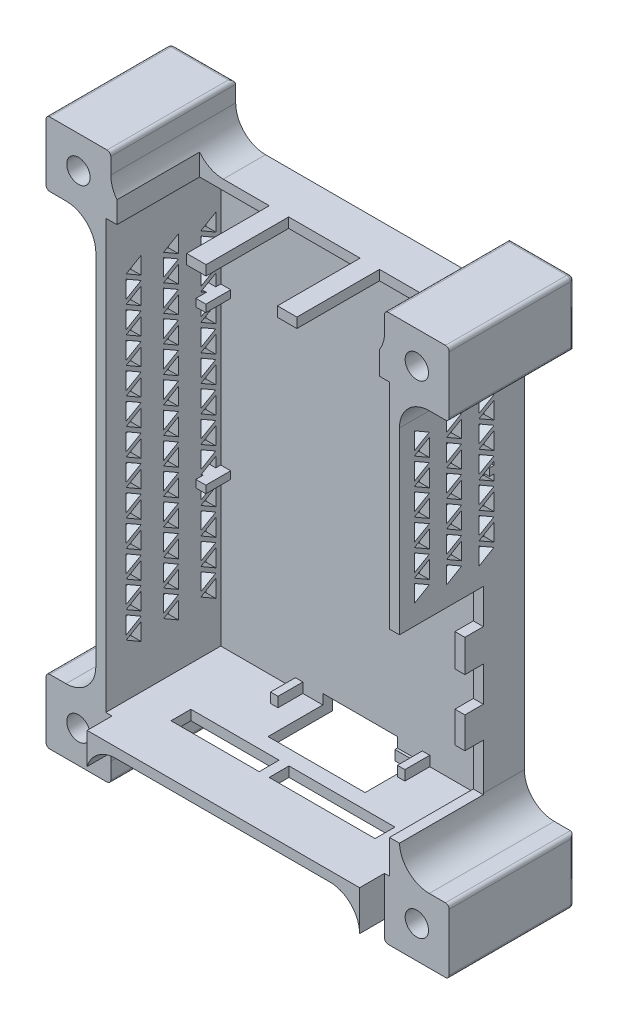
SolidWorks part; units mm, degrees
ref_plane "Front Plane" through (0, 0, 0) normal (0, 0, 1) x (1, 0, 0)
ref_plane "Top Plane" through (0, 0, 0) normal (0, 1, 0) x (1, 0, 0)
ref_plane "Right Plane" through (0, 0, 0) normal (1, 0, 0) x (0, 0, -1)
sketch "Sketch1" plane through (0, 0, 0) normal (0, 0, 1) x (1, 0, 0)
  line L1 (0, 0) -> (61, 0)
  line L2 (0, 0) -> (0, 90)
  line L3 (0, 90) -> (61, 90)
  line L4 (61, 0) -> (61, 90)
  dimension "D1" = 61
  dimension "D2" = 90
extrude "Boss-Extrude1" add sketch "Sketch1" along normal blind 2
sketch "Sketch2" plane through (0, 0, 2) normal (0, 0, 1) x (1, 0, 0)
  line L7 (0, -16.225) -> (0, 16.225) construction
  line L8 (0, 90) -> (0, 0)
  line L9 (2, 90) -> (2, 2)
  line L10 (2, 2) -> (59, 2)
  line L11 (59, 2) -> (59, 90)
  line L12 (2, 88) -> (2, 2)
  line L13 (2, 2) -> (59, 2)
  line L14 (59, 2) -> (59, 88)
  line L15 (0, 0) -> (61, 0)
  line L18 (61, 90) -> (61, 0)
  line L20 (2, 88) -> (59, 88)
  line L21 (0, 90) -> (61, 90)
  dimension "D1" = 2
extrude "Boss-Extrude2" add sketch "Sketch2" along normal blind 6.6
sketch "Sketch3" plane through (0, 0, 2) normal (0, 0, 1) x (1, 0, 0)
  line L0 (59, 2) -> (2, 2) construction
  line L1 (44, 2) -> (42.5, 2)
  line L2 (44, 2) -> (44, 4)
  line L3 (44, 4) -> (42.5, 4)
  line L4 (42.5, 2) -> (42.5, 4)
  line L5 (2, 2) -> (2, 88) construction
  line L6 (17, 2) -> (18.5, 2)
  line L7 (17, 2) -> (17, 4)
  line L8 (17, 4) -> (18.5, 4)
  line L9 (18.5, 2) -> (18.5, 4)
  line L10 (2, 32) -> (4, 32)
  line L11 (2, 32) -> (2, 33.5)
  line L12 (2, 33.5) -> (4, 33.5)
  line L13 (4, 32) -> (4, 33.5)
  line L14 (59, 88) -> (59, 2) construction
  line L15 (59, 32) -> (57, 32)
  line L16 (59, 32) -> (59, 33.5)
  line L17 (59, 33.5) -> (57, 33.5)
  line L18 (57, 32) -> (57, 33.5)
  line L19 (2, 2) -> (2, 88) construction
  line L20 (59, 63.5) -> (57, 63.5)
  line L21 (59, 63.5) -> (59, 65)
  line L22 (59, 65) -> (57, 65)
  line L23 (57, 63.5) -> (57, 65)
  line L24 (2, 63.5) -> (4, 63.5)
  line L25 (2, 63.5) -> (2, 65)
  line L26 (2, 65) -> (4, 65)
  line L27 (4, 63.5) -> (4, 65)
  line L28 (59, 2) -> (2, 2) construction
  dimension "D1" = 1.5
  dimension "D2" = 1.5
  dimension "D3" = 1.5
  dimension "D4" = 1.5
  dimension "D5" = 1.5
  dimension "D6" = 1.5
  dimension "D7" = 2
  dimension "D8" = 2
  dimension "D9" = 2
  dimension "D10" = 2
  dimension "D11" = 2
  dimension "D12" = 2
  dimension "D13" = 30
  dimension "D14" = 30
  dimension "D15" = 30
  dimension "D16" = 30
  dimension "D17" = 15
  dimension "D18" = 15
extrude "Boss-Extrude3" add sketch "Sketch3" along normal blind 5
sketch "Sketch4" plane through (0, 0, 8.6) normal (0, 0, 1) x (1, 0, 0)
  line L1 (61, 90) -> (0, 90)
  line L3 (59, 88) -> (2, 88)
  line L5 (61, 90) -> (61, 0)
  line L6 (0, 90) -> (0, 0)
  line L7 (0, 0) -> (61, 0)
  line L8 (2, 2) -> (59, 2)
  line L9 (2, 88) -> (2, 2)
  line L10 (59, 2) -> (59, 88)
  line L11 (59, 2) -> (59, 88) construction
extrude "Boss-Extrude4" add sketch "Sketch4" along normal blind 16.5
sketch "Sketch5" plane through (0, 90, 0) normal (0, 1, 0) x (1, 0, 0)
  line L1 (57, -8.5) -> (40.4, -8.5)
  line L3 (57, -22.25) -> (40.4, -22.25) construction
  line L4 (40.4, -8.5) -> (40.4, -22.25)
  line L5 (61, 0) -> (0, 0) construction
  line L6 (61, -25.1) -> (0, -25.1) construction
  line L7 (36.5, -25.1) -> (22.15, -25.1)
  line L8 (36.5, -25.1) -> (36.5, -8.5)
  line L9 (36.5, -8.5) -> (22.15, -8.5)
  line L10 (22.15, -25.1) -> (22.15, -8.5)
  line L11 (0, -25.1) -> (0, 0) construction
  line L12 (18.25, -25.1) -> (4.25, -25.1)
  line L13 (18.25, -25.1) -> (18.25, -8.5)
  line L14 (18.25, -8.5) -> (4.25, -8.5)
  line L15 (4.25, -25.1) -> (4.25, -8.5)
  line L17 (57, -25.1) -> (40.4, -25.1)
  line L19 (57, -22.25) -> (40.4, -22.25) construction
  line L20 (40.4, -25.1) -> (40.4, -22.25)
  line L21 (57, -8.5) -> (57, -25.1)
  line L22 (61, -25.1) -> (61, 0) construction
  point P21 (61, -12.55)
  dimension "D2" = 16.6
  dimension "D3" = 13.75
  dimension "D4" = 8.5
  dimension "D5" = 4.25
  dimension "D6" = 3.9
  dimension "D7" = 14
  dimension "D8" = 8.5
  dimension "D9" = 8.5
  dimension "D10" = 3.9
  dimension "D11" = 4
  dimension "D12" = 0
extrude "Cut-Extrude1" cut sketch "Sketch5" against normal blind 2
sketch "Sketch7" plane through (61, 0, 0) normal (1, 0, 0) x (0, 0, -1)
  line L0 (-11.95, 18.25) -> (-11.95, 24.5)
  line L8 (-11.95, 18.25) -> (-8.25, 18.25)
  line L9 (-8.25, 8.75) -> (-8.25, 18.25)
  line L10 (-11.95, 24.5) -> (-8.25, 24.5)
  line L12 (-11.95, 38) -> (-8.25, 38)
  line L14 (-11.95, 31.5) -> (-8.25, 31.5)
  line L18 (-25.1, 0) -> (-25.1, 90) construction
  line L19 (-25.1, 8.75) -> (-25.1, 45)
  line L21 (-11.95, 38) -> (-11.95, 31.5)
  line L22 (-8.25, 8.75) -> (-25.1, 8.75)
  line L23 (-25.1, 45) -> (-8.25, 45)
  line L24 (-25.1, 0) -> (0, 0) construction
  line L25 (-8.25, 24.5) -> (-8.25, 31.5)
  line L26 (-8.25, 38) -> (-8.25, 45)
  line L28 (0, 0) -> (0, 90) construction
  line L47 (-22.1, 79) -> (-19.1, 77.2679)
  line L49 (-19.1, 77.2679) -> (-22.1, 75.5359)
  line L50 (-22.1, 75.5359) -> (-22.1, 79)
  line L141 (-22.1, 74.6121) -> (-19.1, 76.3442)
  line L144 (-19.1, 76.3442) -> (-19.1, 72.8801)
  line L145 (-19.1, 72.8801) -> (-22.1, 74.6121)
  line L146 (-25.1, 90) -> (0, 90) construction
  line L151 (-15.6, 75.5359) -> (-15.6, 79)
  line L152 (-15.6, 79) -> (-12.6, 77.2679)
  line L153 (-12.6, 77.2679) -> (-15.6, 75.5359)
  line L154 (-12.6, 72.8801) -> (-15.6, 74.6121)
  line L155 (-15.6, 74.6121) -> (-12.6, 76.3442)
  line L156 (-12.6, 76.3442) -> (-12.6, 72.8801)
  line L157 (-9.1, 75.5359) -> (-9.1, 79)
  line L158 (-9.1, 79) -> (-6.1, 77.2679)
  line L159 (-6.1, 77.2679) -> (-9.1, 75.5359)
  line L160 (-6.1, 72.8801) -> (-9.1, 74.6121)
  line L161 (-9.1, 74.6121) -> (-6.1, 76.3442)
  line L162 (-6.1, 76.3442) -> (-6.1, 72.8801)
  line L163 (-15.6, 70.2243) -> (-15.6, 73.6884)
  line L164 (-15.6, 73.6884) -> (-12.6, 71.9563)
  line L165 (-12.6, 71.9563) -> (-15.6, 70.2243)
  line L166 (-12.6, 67.5685) -> (-15.6, 69.3005)
  line L167 (-15.6, 69.3005) -> (-12.6, 71.0326)
  line L168 (-12.6, 71.0326) -> (-12.6, 67.5685)
  line L169 (-9.1, 70.2243) -> (-9.1, 73.6884)
  line L170 (-9.1, 73.6884) -> (-6.1, 71.9563)
  line L171 (-6.1, 71.9563) -> (-9.1, 70.2243)
  line L172 (-6.1, 67.5685) -> (-9.1, 69.3005)
  line L173 (-9.1, 69.3005) -> (-6.1, 71.0326)
  line L174 (-6.1, 71.0326) -> (-6.1, 67.5685)
  line L175 (-15.6, 64.9127) -> (-15.6, 68.3768)
  line L176 (-15.6, 68.3768) -> (-12.6, 66.6447)
  line L177 (-12.6, 66.6447) -> (-15.6, 64.9127)
  line L178 (-12.6, 62.2568) -> (-15.6, 63.9889)
  line L179 (-15.6, 63.9889) -> (-12.6, 65.7209)
  line L180 (-12.6, 65.7209) -> (-12.6, 62.2568)
  line L181 (-9.1, 64.9127) -> (-9.1, 68.3768)
  line L182 (-9.1, 68.3768) -> (-6.1, 66.6447)
  line L183 (-6.1, 66.6447) -> (-9.1, 64.9127)
  line L184 (-6.1, 62.2568) -> (-9.1, 63.9889)
  line L185 (-9.1, 63.9889) -> (-6.1, 65.7209)
  line L186 (-6.1, 65.7209) -> (-6.1, 62.2568)
  line L187 (-15.6, 59.601) -> (-15.6, 63.0651)
  line L188 (-15.6, 63.0651) -> (-12.6, 61.3331)
  line L189 (-12.6, 61.3331) -> (-15.6, 59.601)
  line L190 (-12.6, 56.9452) -> (-15.6, 58.6773)
  line L191 (-15.6, 58.6773) -> (-12.6, 60.4093)
  line L192 (-12.6, 60.4093) -> (-12.6, 56.9452)
  line L193 (-9.1, 59.601) -> (-9.1, 63.0651)
  line L194 (-9.1, 63.0651) -> (-6.1, 61.3331)
  line L195 (-6.1, 61.3331) -> (-9.1, 59.601)
  line L196 (-6.1, 56.9452) -> (-9.1, 58.6773)
  line L197 (-9.1, 58.6773) -> (-6.1, 60.4093)
  line L198 (-6.1, 60.4093) -> (-6.1, 56.9452)
  line L199 (-15.6, 54.2894) -> (-15.6, 57.7535)
  line L200 (-15.6, 57.7535) -> (-12.6, 56.0215)
  line L201 (-12.6, 56.0215) -> (-15.6, 54.2894)
  line L202 (-12.6, 51.6336) -> (-15.6, 53.3656)
  line L203 (-15.6, 53.3656) -> (-12.6, 55.0977)
  line L204 (-12.6, 55.0977) -> (-12.6, 51.6336)
  line L205 (-9.1, 54.2894) -> (-9.1, 57.7535)
  line L206 (-9.1, 57.7535) -> (-6.1, 56.0215)
  line L207 (-6.1, 56.0215) -> (-9.1, 54.2894)
  line L208 (-6.1, 51.6336) -> (-9.1, 53.3656)
  line L209 (-9.1, 53.3656) -> (-6.1, 55.0977)
  line L210 (-6.1, 55.0977) -> (-6.1, 51.6336)
  line L211 (-15.6, 48.9778) -> (-15.6, 52.4419)
  line L212 (-15.6, 52.4419) -> (-12.6, 50.7098)
  line L213 (-12.6, 50.7098) -> (-15.6, 48.9778)
  line L217 (-9.1, 48.9778) -> (-9.1, 52.4419)
  line L218 (-9.1, 52.4419) -> (-6.1, 50.7098)
  line L219 (-6.1, 50.7098) -> (-9.1, 48.9778)
  line L223 (-22.1, 70.2243) -> (-22.1, 73.6884)
  line L224 (-22.1, 73.6884) -> (-19.1, 71.9563)
  line L225 (-19.1, 71.9563) -> (-22.1, 70.2243)
  line L226 (-19.1, 67.5685) -> (-22.1, 69.3005)
  line L227 (-22.1, 69.3005) -> (-19.1, 71.0326)
  line L228 (-19.1, 71.0326) -> (-19.1, 67.5685)
  line L229 (-22.1, 64.9127) -> (-22.1, 68.3768)
  line L230 (-22.1, 68.3768) -> (-19.1, 66.6447)
  line L231 (-19.1, 66.6447) -> (-22.1, 64.9127)
  line L232 (-19.1, 62.2568) -> (-22.1, 63.9889)
  line L233 (-22.1, 63.9889) -> (-19.1, 65.7209)
  line L234 (-19.1, 65.7209) -> (-19.1, 62.2568)
  line L235 (-22.1, 59.601) -> (-22.1, 63.0651)
  line L236 (-22.1, 63.0651) -> (-19.1, 61.3331)
  line L237 (-19.1, 61.3331) -> (-22.1, 59.601)
  line L238 (-19.1, 56.9452) -> (-22.1, 58.6773)
  line L239 (-22.1, 58.6773) -> (-19.1, 60.4093)
  line L240 (-19.1, 60.4093) -> (-19.1, 56.9452)
  line L241 (-22.1, 54.2894) -> (-22.1, 57.7535)
  line L242 (-22.1, 57.7535) -> (-19.1, 56.0215)
  line L243 (-19.1, 56.0215) -> (-22.1, 54.2894)
  line L244 (-19.1, 51.6336) -> (-22.1, 53.3656)
  line L245 (-22.1, 53.3656) -> (-19.1, 55.0977)
  line L246 (-19.1, 55.0977) -> (-19.1, 51.6336)
  line L247 (-22.1, 48.9778) -> (-22.1, 52.4419)
  line L248 (-22.1, 52.4419) -> (-19.1, 50.7098)
  line L249 (-19.1, 50.7098) -> (-22.1, 48.9778)
  line L253 (-6.1, 49.7861) -> (-6.1, 46.322) [skipped]
  line L254 (-9.1, 48.054) -> (-6.1, 49.7861) [skipped]
  line L255 (-12.6, 49.7861) -> (-12.6, 46.322) [skipped]
  line L256 (-15.6, 48.054) -> (-12.6, 49.7861) [skipped]
  line L257 (-19.1, 49.7861) -> (-19.1, 46.322) [skipped]
  line L258 (-22.1, 48.054) -> (-19.1, 49.7861) [skipped]
  line L259 (-19.1, 46.322) -> (-22.1, 48.054) [skipped]
  line L260 (-12.6, 46.322) -> (-15.6, 48.054) [skipped]
  line L261 (-6.1, 46.322) -> (-9.1, 48.054) [skipped]
  point P0 (-8.25, 13.5)
  point P16 (-8.25, 41.5)
  point P18 (-10.1, 18.25)
  point P20 (-8.25, 28)
  dimension "D1" = 9.5
  dimension "D2" = 28
  dimension "D3" = 7
  dimension "D4" = 7
  dimension "D5" = 13.5
  dimension "D6" = 41.5
  dimension "D7" = 3.7
  dimension "D8" = 3.7
  dimension "D9" = 8.25
  dimension "D10" = 0
  dimension "D11" = 0
  dimension "D12" = 60
  dimension "D13" = 60
  dimension "D14" = 60
  dimension "D15" = 60
  dimension "D16" = 0.9238
  dimension "D17" = 3
  dimension "D18" = 11
  dimension "D19" = 3
  dimension "D20" = 3
  dimension "D21" = 6
  dimension "D22" = 0.9238
  dimension "D23" = 3
  dimension "D24" = 9.5
sketch "Sketch8" plane through (0, 0, 0) normal (0, -1, 0) x (-1, 0, 0)
  line L0 (0, -25.1) -> (0, 0) construction
  line L2 (-22.5, -13) -> (-22.5, -2.5)
  line L3 (-22.5, -2.5) -> (-42, -2.5)
  line L4 (-42, -13) -> (-42, -2.5)
  line L5 (0, 13.805) -> (0, -13.805) construction
  line L6 (-61, -25.1) -> (-61, 0) construction
  line L7 (-33.55, 0) -> (33.55, 0) construction
  line L8 (-22.5, -13) -> (-42, -13)
  line L9 (-10, -20) -> (-27.72, -20)
  line L10 (-10, -20) -> (-10, -16)
  line L11 (-10, -16) -> (-27.72, -16)
  line L12 (-51, -20) -> (-51, -16)
  line L13 (-27.72, -20) -> (-27.72, -16)
  line L14 (-29.72, -20) -> (-29.72, -16)
  line L15 (-29.72, -20) -> (-51, -20)
  line L16 (-29.72, -16) -> (-51, -16)
  dimension "D1" = 22.5
  dimension "D2" = 19
  dimension "D3" = 2.5
  dimension "D4" = 10.5
  dimension "D5" = 3
  dimension "D6" = 4
  dimension "D7" = 10
  dimension "D8" = 10
  dimension "D9" = 2
  dimension "D10" = 31.28
extrude "Cut-Extrude3" cut sketch "Sketch8" against normal blind 2
sketch "Sketch9" plane through (0, 0, 0) normal (-1, 0, 0) x (0, 0, 1)
  line L0 (3, 78) -> (6, 76.2679)
  line L5 (6, 76.2679) -> (3, 74.5359)
  line L6 (3, 74.5359) -> (3, 78)
  line L7 (3, 73.6121) -> (6, 75.3442)
  line L20 (6, 75.3442) -> (6, 71.8801)
  line L22 (6, 71.8801) -> (3, 73.6121)
  line L24 (0, 90) -> (0, 0) construction
  line L215 (25.1, 90) -> (0, 90) construction
  line L232 (10.5, 74.5359) -> (10.5, 78)
  line L236 (10.5, 78) -> (13.5, 76.2679)
  line L238 (13.5, 76.2679) -> (10.5, 74.5359)
  line L267 (13.5, 71.8801) -> (10.5, 73.6121)
  line L268 (10.5, 73.6121) -> (13.5, 75.3442)
  line L269 (13.5, 75.3442) -> (13.5, 71.8801)
  line L270 (18, 74.5359) -> (18, 78)
  line L271 (18, 78) -> (21, 76.2679)
  line L272 (21, 76.2679) -> (18, 74.5359)
  line L273 (21, 71.8801) -> (18, 73.6121)
  line L274 (18, 73.6121) -> (21, 75.3442)
  line L275 (21, 75.3442) -> (21, 71.8801)
  line L276 (10.5, 69.2243) -> (10.5, 72.6884)
  line L277 (10.5, 72.6884) -> (13.5, 70.9563)
  line L278 (13.5, 70.9563) -> (10.5, 69.2243)
  line L279 (13.5, 66.5685) -> (10.5, 68.3005)
  line L280 (10.5, 68.3005) -> (13.5, 70.0326)
  line L281 (13.5, 70.0326) -> (13.5, 66.5685)
  line L282 (18, 69.2243) -> (18, 72.6884)
  line L283 (18, 72.6884) -> (21, 70.9563)
  line L284 (21, 70.9563) -> (18, 69.2243)
  line L285 (21, 66.5685) -> (18, 68.3005)
  line L286 (18, 68.3005) -> (21, 70.0326)
  line L287 (21, 70.0326) -> (21, 66.5685)
  line L288 (10.5, 63.9127) -> (10.5, 67.3768)
  line L289 (10.5, 67.3768) -> (13.5, 65.6447)
  line L290 (13.5, 65.6447) -> (10.5, 63.9127)
  line L291 (13.5, 61.2568) -> (10.5, 62.9889)
  line L292 (10.5, 62.9889) -> (13.5, 64.7209)
  line L293 (13.5, 64.7209) -> (13.5, 61.2568)
  line L294 (18, 63.9127) -> (18, 67.3768)
  line L295 (18, 67.3768) -> (21, 65.6447)
  line L296 (21, 65.6447) -> (18, 63.9127)
  line L297 (21, 61.2568) -> (18, 62.9889)
  line L298 (18, 62.9889) -> (21, 64.7209)
  line L299 (21, 64.7209) -> (21, 61.2568)
  line L300 (10.5, 58.601) -> (10.5, 62.0651)
  line L301 (10.5, 62.0651) -> (13.5, 60.3331)
  line L302 (13.5, 60.3331) -> (10.5, 58.601)
  line L303 (13.5, 55.9452) -> (10.5, 57.6773)
  line L304 (10.5, 57.6773) -> (13.5, 59.4093)
  line L305 (13.5, 59.4093) -> (13.5, 55.9452)
  line L306 (18, 58.601) -> (18, 62.0651)
  line L307 (18, 62.0651) -> (21, 60.3331)
  line L308 (21, 60.3331) -> (18, 58.601)
  line L309 (21, 55.9452) -> (18, 57.6773)
  line L310 (18, 57.6773) -> (21, 59.4093)
  line L311 (21, 59.4093) -> (21, 55.9452)
  line L312 (10.5, 53.2894) -> (10.5, 56.7535)
  line L313 (10.5, 56.7535) -> (13.5, 55.0215)
  line L314 (13.5, 55.0215) -> (10.5, 53.2894)
  line L315 (13.5, 50.6336) -> (10.5, 52.3656)
  line L316 (10.5, 52.3656) -> (13.5, 54.0977)
  line L317 (13.5, 54.0977) -> (13.5, 50.6336)
  line L318 (18, 53.2894) -> (18, 56.7535)
  line L319 (18, 56.7535) -> (21, 55.0215)
  line L320 (21, 55.0215) -> (18, 53.2894)
  line L321 (21, 50.6336) -> (18, 52.3656)
  line L322 (18, 52.3656) -> (21, 54.0977)
  line L323 (21, 54.0977) -> (21, 50.6336)
  line L324 (10.5, 47.9778) -> (10.5, 51.4419)
  line L325 (10.5, 51.4419) -> (13.5, 49.7098)
  line L326 (13.5, 49.7098) -> (10.5, 47.9778)
  line L327 (13.5, 45.322) -> (10.5, 47.054)
  line L328 (10.5, 47.054) -> (13.5, 48.7861)
  line L329 (13.5, 48.7861) -> (13.5, 45.322)
  line L330 (18, 47.9778) -> (18, 51.4419)
  line L331 (18, 51.4419) -> (21, 49.7098)
  line L332 (21, 49.7098) -> (18, 47.9778)
  line L333 (21, 45.322) -> (18, 47.054)
  line L334 (18, 47.054) -> (21, 48.7861)
  line L335 (21, 48.7861) -> (21, 45.322)
  line L336 (10.5, 42.6662) -> (10.5, 46.1303)
  line L337 (10.5, 46.1303) -> (13.5, 44.3982)
  line L338 (13.5, 44.3982) -> (10.5, 42.6662)
  line L339 (13.5, 40.0104) -> (10.5, 41.7424)
  line L340 (10.5, 41.7424) -> (13.5, 43.4745)
  line L341 (13.5, 43.4745) -> (13.5, 40.0104)
  line L342 (18, 42.6662) -> (18, 46.1303)
  line L343 (18, 46.1303) -> (21, 44.3982)
  line L344 (21, 44.3982) -> (18, 42.6662)
  line L345 (21, 40.0104) -> (18, 41.7424)
  line L346 (18, 41.7424) -> (21, 43.4745)
  line L347 (21, 43.4745) -> (21, 40.0104)
  line L348 (10.5, 37.3545) -> (10.5, 40.8186)
  line L349 (10.5, 40.8186) -> (13.5, 39.0866)
  line L350 (13.5, 39.0866) -> (10.5, 37.3545)
  line L351 (13.5, 34.6987) -> (10.5, 36.4308)
  line L352 (10.5, 36.4308) -> (13.5, 38.1628)
  line L353 (13.5, 38.1628) -> (13.5, 34.6987)
  line L354 (18, 37.3545) -> (18, 40.8186)
  line L355 (18, 40.8186) -> (21, 39.0866)
  line L356 (21, 39.0866) -> (18, 37.3545)
  line L357 (21, 34.6987) -> (18, 36.4308)
  line L358 (18, 36.4308) -> (21, 38.1628)
  line L359 (21, 38.1628) -> (21, 34.6987)
  line L360 (10.5, 32.0429) -> (10.5, 35.507)
  line L361 (10.5, 35.507) -> (13.5, 33.775)
  line L362 (13.5, 33.775) -> (10.5, 32.0429)
  line L363 (13.5, 29.3871) -> (10.5, 31.1192)
  line L364 (10.5, 31.1192) -> (13.5, 32.8512)
  line L365 (13.5, 32.8512) -> (13.5, 29.3871)
  line L366 (18, 32.0429) -> (18, 35.507)
  line L367 (18, 35.507) -> (21, 33.775)
  line L368 (21, 33.775) -> (18, 32.0429)
  line L369 (21, 29.3871) -> (18, 31.1192)
  line L370 (18, 31.1192) -> (21, 32.8512)
  line L371 (21, 32.8512) -> (21, 29.3871)
  line L372 (10.5, 26.7313) -> (10.5, 30.1954)
  line L373 (10.5, 30.1954) -> (13.5, 28.4633)
  line L374 (13.5, 28.4633) -> (10.5, 26.7313)
  line L375 (13.5, 24.0755) -> (10.5, 25.8075)
  line L376 (10.5, 25.8075) -> (13.5, 27.5396)
  line L377 (13.5, 27.5396) -> (13.5, 24.0755)
  line L378 (18, 26.7313) -> (18, 30.1954)
  line L379 (18, 30.1954) -> (21, 28.4633)
  line L380 (21, 28.4633) -> (18, 26.7313)
  line L381 (21, 24.0755) -> (18, 25.8075)
  line L382 (18, 25.8075) -> (21, 27.5396)
  line L383 (21, 27.5396) -> (21, 24.0755)
  line L384 (10.5, 21.4197) -> (10.5, 24.8838)
  line L385 (10.5, 24.8838) -> (13.5, 23.1517)
  line L386 (13.5, 23.1517) -> (10.5, 21.4197)
  line L387 (13.5, 18.7639) -> (10.5, 20.4959)
  line L388 (10.5, 20.4959) -> (13.5, 22.228)
  line L389 (13.5, 22.228) -> (13.5, 18.7639)
  line L390 (18, 21.4197) -> (18, 24.8838)
  line L391 (18, 24.8838) -> (21, 23.1517)
  line L392 (21, 23.1517) -> (18, 21.4197)
  line L393 (21, 18.7639) -> (18, 20.4959)
  line L394 (18, 20.4959) -> (21, 22.228)
  line L395 (21, 22.228) -> (21, 18.7639)
  line L396 (10.5, 16.1081) -> (10.5, 19.5722)
  line L397 (10.5, 19.5722) -> (13.5, 17.8401)
  line L398 (13.5, 17.8401) -> (10.5, 16.1081)
  line L399 (13.5, 13.4522) -> (10.5, 15.1843)
  line L400 (10.5, 15.1843) -> (13.5, 16.9163)
  line L401 (13.5, 16.9163) -> (13.5, 13.4522)
  line L402 (18, 16.1081) -> (18, 19.5722)
  line L403 (18, 19.5722) -> (21, 17.8401)
  line L404 (21, 17.8401) -> (18, 16.1081)
  line L405 (21, 13.4522) -> (18, 15.1843)
  line L406 (18, 15.1843) -> (21, 16.9163)
  line L407 (21, 16.9163) -> (21, 13.4522)
  line L408 (10.5, 10.7964) -> (10.5, 14.2605)
  line L409 (10.5, 14.2605) -> (13.5, 12.5285)
  line L410 (13.5, 12.5285) -> (10.5, 10.7964)
  line L414 (18, 10.7964) -> (18, 14.2605)
  line L415 (18, 14.2605) -> (21, 12.5285)
  line L416 (21, 12.5285) -> (18, 10.7964)
  line L420 (3, 69.2243) -> (3, 72.6884)
  line L421 (3, 72.6884) -> (6, 70.9563)
  line L422 (6, 70.9563) -> (3, 69.2243)
  line L423 (6, 66.5685) -> (3, 68.3005)
  line L424 (3, 68.3005) -> (6, 70.0326)
  line L425 (6, 70.0326) -> (6, 66.5685)
  line L426 (3, 63.9127) -> (3, 67.3768)
  line L427 (3, 67.3768) -> (6, 65.6447)
  line L428 (6, 65.6447) -> (3, 63.9127)
  line L429 (6, 61.2568) -> (3, 62.9889)
  line L430 (3, 62.9889) -> (6, 64.7209)
  line L431 (6, 64.7209) -> (6, 61.2568)
  line L432 (3, 58.601) -> (3, 62.0651)
  line L433 (3, 62.0651) -> (6, 60.3331)
  line L434 (6, 60.3331) -> (3, 58.601)
  line L435 (6, 55.9452) -> (3, 57.6773)
  line L436 (3, 57.6773) -> (6, 59.4093)
  line L437 (6, 59.4093) -> (6, 55.9452)
  line L438 (3, 53.2894) -> (3, 56.7535)
  line L439 (3, 56.7535) -> (6, 55.0215)
  line L440 (6, 55.0215) -> (3, 53.2894)
  line L441 (6, 50.6336) -> (3, 52.3656)
  line L442 (3, 52.3656) -> (6, 54.0977)
  line L443 (6, 54.0977) -> (6, 50.6336)
  line L444 (3, 47.9778) -> (3, 51.4419)
  line L445 (3, 51.4419) -> (6, 49.7098)
  line L446 (6, 49.7098) -> (3, 47.9778)
  line L447 (6, 45.322) -> (3, 47.054)
  line L448 (3, 47.054) -> (6, 48.7861)
  line L449 (6, 48.7861) -> (6, 45.322)
  line L450 (3, 42.6662) -> (3, 46.1303)
  line L451 (3, 46.1303) -> (6, 44.3982)
  line L452 (6, 44.3982) -> (3, 42.6662)
  line L453 (6, 40.0104) -> (3, 41.7424)
  line L454 (3, 41.7424) -> (6, 43.4745)
  line L455 (6, 43.4745) -> (6, 40.0104)
  line L456 (3, 37.3545) -> (3, 40.8186)
  line L457 (3, 40.8186) -> (6, 39.0866)
  line L458 (6, 39.0866) -> (3, 37.3545)
  line L459 (6, 34.6987) -> (3, 36.4308)
  line L460 (3, 36.4308) -> (6, 38.1628)
  line L461 (6, 38.1628) -> (6, 34.6987)
  line L462 (3, 32.0429) -> (3, 35.507)
  line L463 (3, 35.507) -> (6, 33.775)
  line L464 (6, 33.775) -> (3, 32.0429)
  line L465 (6, 29.3871) -> (3, 31.1192)
  line L466 (3, 31.1192) -> (6, 32.8512)
  line L467 (6, 32.8512) -> (6, 29.3871)
  line L468 (3, 26.7313) -> (3, 30.1954)
  line L469 (3, 30.1954) -> (6, 28.4633)
  line L470 (6, 28.4633) -> (3, 26.7313)
  line L471 (6, 24.0755) -> (3, 25.8075)
  line L472 (3, 25.8075) -> (6, 27.5396)
  line L473 (6, 27.5396) -> (6, 24.0755)
  line L474 (3, 21.4197) -> (3, 24.8838)
  line L475 (3, 24.8838) -> (6, 23.1517)
  line L476 (6, 23.1517) -> (3, 21.4197)
  line L477 (6, 18.7639) -> (3, 20.4959)
  line L478 (3, 20.4959) -> (6, 22.228)
  line L479 (6, 22.228) -> (6, 18.7639)
  line L480 (3, 16.1081) -> (3, 19.5722)
  line L481 (3, 19.5722) -> (6, 17.8401)
  line L482 (6, 17.8401) -> (3, 16.1081)
  line L483 (6, 13.4522) -> (3, 15.1843)
  line L484 (3, 15.1843) -> (6, 16.9163)
  line L485 (6, 16.9163) -> (6, 13.4522)
  line L486 (3, 10.7964) -> (3, 14.2605)
  line L487 (3, 14.2605) -> (6, 12.5285)
  line L488 (6, 12.5285) -> (3, 10.7964)
  line L492 (6, 11.6047) -> (6, 8.1406) [skipped]
  line L493 (6, 8.1406) -> (3, 9.8727) [skipped]
  line L494 (3, 9.8727) -> (6, 11.6047) [skipped]
  line L495 (10.5, 9.8727) -> (13.5, 11.6047) [skipped]
  line L496 (13.5, 8.1406) -> (10.5, 9.8727) [skipped]
  line L497 (13.5, 11.6047) -> (13.5, 8.1406) [skipped]
  line L498 (21, 8.1406) -> (18, 9.8727) [skipped]
  line L499 (18, 9.8727) -> (21, 11.6047) [skipped]
  line L500 (21, 11.6047) -> (21, 8.1406) [skipped]
  point P10 (4.5, 72.7461)
  dimension "D1" = 60
  dimension "D2" = 60
  dimension "D3" = 12
  dimension "D4" = 3
  dimension "D5" = 0.8
  dimension "D6" = 60
  dimension "D7" = 3
  dimension "D8" = 10.5
  dimension "D9" = 3
  dimension "D10" = 13
  dimension "D11" = 0.8
  dimension "D12" = 3
extrude "Cut-Extrude22" cut sketch "Sketch9" against normal blind 2
sketch "Sketch10" plane through (0, 0, 25.1) normal (0, 0, 1) x (1, 0, 0)
  line L0 (61, 0) -> (61, 8.75) construction
  line L1 (0, 0) -> (61, 0)
  line L2 (0, 0) -> (0, 2)
  line L3 (0, 2) -> (61, 2)
  line L4 (61, 0) -> (61, 2)
  dimension "D1" = 2
extrude "Boss-Extrude5" add sketch "Sketch10" along normal blind 5
sketch "Sketch20" plane through (0, 0, 0) normal (0, 0, -1) x (-1, 0, 0)
  line L0 (-61, 90) -> (0, 90) construction
  line L1 (-3, 3) -> (10, 3)
  line L2 (-3, 3) -> (-3, -10)
  line L3 (-3, -10) -> (10, -10)
  line L4 (10, 3) -> (10, -10)
  line L5 (-3, 3) -> (10, -10) construction
  line L6 (-3, -10) -> (10, 3) construction
  line L7 (-58, 87) -> (-71, 87)
  line L8 (-58, 87) -> (-58, 100)
  line L9 (-58, 100) -> (-71, 100)
  line L10 (-71, 87) -> (-71, 100)
  line L11 (-58, 87) -> (-71, 100) construction
  line L12 (-58, 100) -> (-71, 87) construction
  line L13 (-61, 0) -> (-61, 90) construction
  line L14 (0, 0) -> (-61, 0) construction
  line L15 (0, 90) -> (0, 0) construction
  point P4 (3.5, -3.5)
  point P9 (-64.5, 93.5)
  dimension "D1" = 3
  dimension "D2" = 3
  dimension "D3" = 13
  dimension "D4" = 13
  dimension "D5" = 3
  dimension "D6" = 13
  dimension "D7" = 3
  dimension "D8" = 13
extrude "Boss-Extrude8" add sketch "Sketch20" against normal up to surface (25.1 mm away) up to face at (2.0833, 60, 25.1)
sketch "Sketch25" plane through (0, 0, 25.1) normal (0, 0, 1) x (1, 0, 0)
  line L1 (3, 3) -> (-10, 3)
  line L2 (3, 3) -> (3, -10)
  line L3 (3, -10) -> (-10, -10)
  line L4 (-10, 3) -> (-10, -10)
  line L5 (3, 3) -> (-10, -10) construction
  line L6 (3, -10) -> (-10, 3) construction
  line L7 (3, -10) -> (3.25, -10)
  line L8 (3, -10) -> (3, 3)
  line L9 (3, 3) -> (3.25, 3)
  line L10 (3.25, -10) -> (3.25, 3)
  line L11 (3, -10) -> (3.25, 3) construction
  line L12 (3, 3) -> (3.25, -10) construction
  point P4 (-3.5, -3.5)
  point P10 (3.125, -3.5)
  dimension "D1" = 0.25
extrude "Cut-Extrude11" cut sketch "Sketch25" along normal through all contours L2 L1 L4 L3 | L8 L7 L10 L9
sketch "Sketch26" plane through (0, 0, 25.1) normal (0, 0, 1) x (1, 0, 0)
  line L1 (3, 3) -> (2, 3)
  line L2 (3, 3) -> (3, 2)
  line L3 (3, 2) -> (2, 2)
  line L4 (2, 3) -> (2, 2)
  line L5 (3, 3) -> (2, 2) construction
  line L6 (3, 2) -> (2, 3) construction
  line L7 (58, 87) -> (59, 87)
  line L8 (58, 87) -> (58, 88)
  line L9 (58, 88) -> (59, 88)
  line L10 (59, 87) -> (59, 88)
  line L11 (58, 87) -> (59, 88) construction
  line L12 (58, 88) -> (59, 87) construction
  point P4 (2.5, 2.5)
  point P10 (58.5, 87.5)
  dimension "D1" = 1
  dimension "D2" = 1
  dimension "D3" = 1
  dimension "D4" = 1
extrude "Cut-Extrude12" cut sketch "Sketch26" against normal up to surface (23.1 mm away) up to face at (30.5, 36.25, 2)
sketch "Sketch27" plane through (0, 0, 25.1) normal (0, 0, 1) x (1, 0, 0)
  line L0 (64.5, 100) -> (64.5, 87) construction
  line L1 (58, 100) -> (71, 100) construction
  line L2 (71, 87) -> (61, 87) construction
  line L3 (71, 93.5) -> (58, 93.5) construction
  line L4 (71, 100) -> (71, 87) construction
  line L5 (58, 90) -> (58, 100) construction
  line L6 (-3.5, -10) -> (-3.5, 3) construction
  line L7 (3, -10) -> (-10, -10) construction
  line L8 (-10, 3) -> (0, 3) construction
  line L9 (-10, -3.5) -> (3, -3.5) construction
  line L10 (-10, -10) -> (-10, 3) construction
  line L11 (3, 0) -> (3, -10) construction
  circle A0 centre (-3.5, -3.5) radius 2.35
  circle A1 centre (64.5, 93.5) radius 2.35
  dimension "D1" = 4.7
  dimension "D2" = 4.7
extrude "Cut-Extrude13" cut sketch "Sketch27" against normal through all
sketch "Sketch31" plane through (0, 0, 0) normal (0, 0, -1) x (-1, 0, 0)
  line L0 (-71, 100) -> (-71, 87) construction
  line L1 (-61.8731, 88.95) -> (-59.2461, 93.5)
  line L2 (-59.2461, 93.5) -> (-61.8731, 98.05)
  line L3 (-61.8731, 98.05) -> (-67.1269, 98.05)
  line L4 (-67.1269, 98.05) -> (-69.7539, 93.5)
  line L5 (-69.7539, 93.5) -> (-67.1269, 88.95)
  line L6 (-67.1269, 88.95) -> (-61.8731, 88.95)
  line L7 (6.1269, -8.05) -> (8.7539, -3.5)
  line L8 (8.7539, -3.5) -> (6.1269, 1.05)
  line L9 (6.1269, 1.05) -> (0.8731, 1.05)
  line L10 (0.8731, 1.05) -> (-1.7539, -3.5)
  line L11 (-1.7539, -3.5) -> (0.8731, -8.05)
  line L12 (0.8731, -8.05) -> (6.1269, -8.05)
  line L13 (10, -10) -> (10, 3) construction
  circle A0 centre (-64.5, 93.5) radius 4.55 construction
  circle A1 centre (3.5, -3.5) radius 4.55 construction
  dimension "D1" = 9.1
  dimension "D2" = 9.1
  dimension "D3" = 30
  dimension "D4" = 30
extrude "Cut-Extrude17" cut sketch "Sketch31" against normal blind 6
fillet "Fillet3" radius 6 1 edges at (58, 90, 12.55) type face fillet first side face at (29.5687, 90, 15.7375) second side face at (58, 95, 12.55)
sketch "Sketch33" plane through (0, 0, 25.1) normal (0, 0, 1) x (1, 0, 0)
  line L0 (2, 2) -> (3.25, 2) construction
  line L1 (3.25, 0) -> (3, 0)
  line L2 (3.25, 0) -> (3.25, 2)
  line L3 (3.25, 2) -> (3, 2)
  line L4 (3, 0) -> (3, 2)
  line L5 (3.25, 0) -> (3, 2) construction
  line L6 (3.25, 2) -> (3, 0) construction
  point P4 (3.125, 1)
  dimension "D1" = 0.25
fillet "Fillet7" radius 6 1 edges at (3, 0, 12.55) type face fillet first side face at (3, -5, 12.55) second side face at (18.86, 0, 18)
sketch "Sketch34" plane through (0, 0, 25.1) normal (0, 0, 1) x (1, 0, 0)
  line L0 (18.25, 90) -> (4.25, 90) construction
  line L1 (59, 3) -> (71, 3)
  line L2 (58, 2) -> (58, -10)
  line L3 (58, -10) -> (71, -10)
  line L4 (71, 3) -> (71, -10)
  line L5 (59, 2) -> (71, -10) construction
  line L6 (58, -10) -> (71, 3) construction
  line L7 (2, 87) -> (-10, 87)
  line L8 (3, 88) -> (3, 100)
  line L9 (3, 100) -> (-10, 100)
  line L10 (-10, 87) -> (-10, 100)
  line L11 (2, 88) -> (-10, 100) construction
  line L12 (3, 100) -> (-10, 87) construction
  line L13 (0, 90) -> (0, 3) construction
  line L14 (61, 0) -> (61, 2) construction
  line L15 (9, 0) -> (61, 0) construction
  line L16 (59, 88) -> (2, 88) construction
  line L17 (2, 88) -> (2, 2) construction
  line L18 (3, 88) -> (2, 88)
  line L19 (2, 88) -> (2, 87)
  line L20 (59, 2) -> (59, 88) construction
  line L21 (44, 2) -> (59, 2) construction
  line L22 (59, 2) -> (59, 3)
  line L23 (58, 2) -> (59, 2)
  point P4 (64.5, -3.5)
  point P9 (-3.5, 93.5)
  dimension "D1" = 3
  dimension "D2" = 3
  dimension "D3" = 3
  dimension "D4" = 3
  dimension "D5" = 13
  dimension "D6" = 13
  dimension "D7" = 13
  dimension "D8" = 13
extrude "Boss-Extrude11" add sketch "Sketch34" against normal up to surface (25.1 mm away) up to face at (30.5, 45, 0)
sketch "Sketch35" plane through (0, 0, 25.1) normal (0, 0, 1) x (1, 0, 0)
  line L0 (-3.5, 100) -> (-3.5, 87) construction
  line L1 (3, 100) -> (-10, 100) construction
  line L2 (-10, 87) -> (0, 87) construction
  line L3 (-10, 93.5) -> (3, 93.5) construction
  line L4 (-10, 100) -> (-10, 87) construction
  line L5 (3, 90) -> (3, 100) construction
  line L6 (64.5, -10) -> (64.5, 3) construction
  line L7 (58, -10) -> (71, -10) construction
  line L8 (71, 3) -> (61, 3) construction
  line L9 (71, -3.5) -> (58, -3.5) construction
  line L10 (71, -10) -> (71, 3) construction
  line L11 (58, 0) -> (58, -10) construction
  circle A0 centre (-3.5, 93.5) radius 2.35
  circle A1 centre (64.5, -3.5) radius 2.35
  dimension "D1" = 4.7
  dimension "D2" = 4.7
extrude "Cut-Extrude18" cut sketch "Sketch35" against normal through all
fillet "Fillet10" radius 6 1 edges at (3, 90, 12.55) type face fillet first side face at (3, 95, 12.55) second side face at (25.2214, 90, 14.4)
fillet "Fillet13" radius 0.75 20 edges at (71, -3.5, 0) (64.5, -10, 0) (-3.5, -10, 0) (-10, -3.5, 0) (-10, 93.5, 0) (-3.5, 100, 0) (71, 93.5, 0) (64.5, 100, 0) (71, 87, 12.55) (71, 100, 12.55) (58, 100, 12.55) (3, 100, 12.55) (-10, 100, 12.55) (-10, 87, 12.55) (-10, 3, 12.55) (-10, -10, 12.55) (3, -10, 12.55) (71, 3, 12.55) (58, -10, 12.55) (71, -10, 12.55)
sketch "Sketch36" plane through (0, 0, 0) normal (0, 0, -1) x (-1, 0, 0)
  line L0 (10, 99.25) -> (10, 87.75) construction
  line L1 (-59.2461, -3.5) -> (-61.8731, 1.05)
  line L2 (-61.8731, 1.05) -> (-67.1269, 1.05)
  line L3 (-67.1269, 1.05) -> (-69.7539, -3.5)
  line L4 (-69.7539, -3.5) -> (-67.1269, -8.05)
  line L5 (-67.1269, -8.05) -> (-61.8731, -8.05)
  line L6 (-61.8731, -8.05) -> (-59.2461, -3.5)
  line L7 (-1.7539, 93.5) -> (0.8731, 88.95)
  line L8 (0.8731, 88.95) -> (6.1269, 88.95)
  line L9 (6.1269, 88.95) -> (8.7539, 93.5)
  line L10 (8.7539, 93.5) -> (6.1269, 98.05)
  line L11 (6.1269, 98.05) -> (0.8731, 98.05)
  line L12 (0.8731, 98.05) -> (-1.7539, 93.5)
  line L15 (-70.25, 3) -> (-70.25, -9.25) construction
  circle A0 centre (-64.5, -3.5) radius 4.55 construction
  circle A1 centre (3.5, 93.5) radius 4.55 construction
  dimension "D1" = 30
  dimension "D2" = 30
  dimension "D3" = 9.1
  dimension "D4" = 9.1
extrude "Cut-Extrude19" cut sketch "Sketch36" against normal blind 6
sketch "Sketch38" plane through (0, 0, 25.1) normal (0, 0, 1) x (1, 0, 0)
  line L0 (61, 2) -> (3.25, 2) construction
  line L1 (69, -8) -> (58, -8)
  line L2 (69, -8) -> (69, 3)
  line L3 (69, 3) -> (58, 3)
  line L4 (58, -8) -> (58, 3)
  line L6 (61, 0) -> (61, 2) construction
  dimension "D1" = 11
  dimension "D2" = 8
  dimension "D3" = 1
extrude "Cut-Extrude20" cut sketch "Sketch38" along normal blind 10
fillet "Fillet14" radius 6 1 edges at (58, 0, 12.55) type face fillet first side face at (40.36, 0, 18) second side face at (58, -4.625, 12.55)
sketch "Sketch39" plane through (0, 0, 0) normal (0, -1, 0) x (1, 0, 0)
  line L0 (9, 0) -> (52, 0) construction
  line L1 (22.5, 2.5) -> (37.5, 2.5)
  line L2 (22.5, 2.5) -> (22.5, 0)
  line L3 (22.5, 0) -> (37.5, 0)
  line L4 (37.5, 2.5) -> (37.5, 0)
  dimension "D1" = 15
extrude "Cut-Extrude21" cut sketch "Sketch39" against normal blind 4
fillet "Fillet17" radius 6 1 edges at (0, 87, 12.55) type face fillet first side face at (0, 70.9563, 19) second side face at (-4.625, 87, 12.55)
fillet "Fillet18" radius 6 1 edges at (0, 3, 12.55) type face fillet first side face at (0, 70.9563, 19) second side face at (-4.625, 3, 12.55)
sketch "Sketch43" plane through (0, 0, 0) normal (-1, 0, 0) x (0, 0, 1)
  line L0 (6, 61.2568) -> (6, 64.7209) construction
  line L1 (3, 33.5) -> (6, 33.5)
  line L2 (3, 33.5) -> (3, 32)
  line L3 (3, 32) -> (6, 32)
  line L4 (6, 33.5) -> (6, 32)
  line L5 (3, 33.5) -> (6, 32) construction
  line L6 (3, 32) -> (6, 33.5) construction
  line L7 (3, 65) -> (6, 65)
  line L8 (3, 65) -> (3, 63.5)
  line L9 (3, 63.5) -> (6, 63.5)
  line L10 (6, 65) -> (6, 63.5)
  line L11 (3, 65) -> (6, 63.5) construction
  line L12 (3, 63.5) -> (6, 65) construction
  line L13 (6, 63.5) -> (6, 64.7209) construction
  point P4 (4.5, 32.75)
  point P11 (4.5, 64.25)
  dimension "D1" = 1.5
extrude "Boss-Extrude15" add sketch "Sketch43" against normal up to surface (2 mm away) up to face at (2, 47.9663, 5.8221)
extrude "Cut-Extrude23" cut sketch "Sketch7" against normal blind 2
sketch "Sketch44" plane through (61, 0, 0) normal (1, 0, 0) x (0, 0, -1)
  line L1 (-7, 65) -> (-6.1, 65)
  line L2 (-7, 65) -> (-7, 63.5)
  line L3 (-7, 63.5) -> (-6.1, 63.5)
  line L4 (-6.1, 65) -> (-6.1, 63.5)
  line L5 (-7, 65) -> (-6.1, 63.5) construction
  line L6 (-7, 63.5) -> (-6.1, 65) construction
  point P4 (-6.55, 64.25)
extrude "Boss-Extrude16" add sketch "Sketch44" against normal up to surface (2 mm away) up to face at (59, 50.7098, 21.1)
fillet "Fillet19" radius 6 1 edges at (61, 3, 12.55) type face fillet first side face at (61, 66.6447, 21.1) second side face at (65.625, 3, 12.55)
fillet "Fillet20" radius 6 1 edges at (61, 87, 12.55) type face fillet first side face at (61, 66.6447, 21.1) second side face at (65.625, 87, 12.55)
